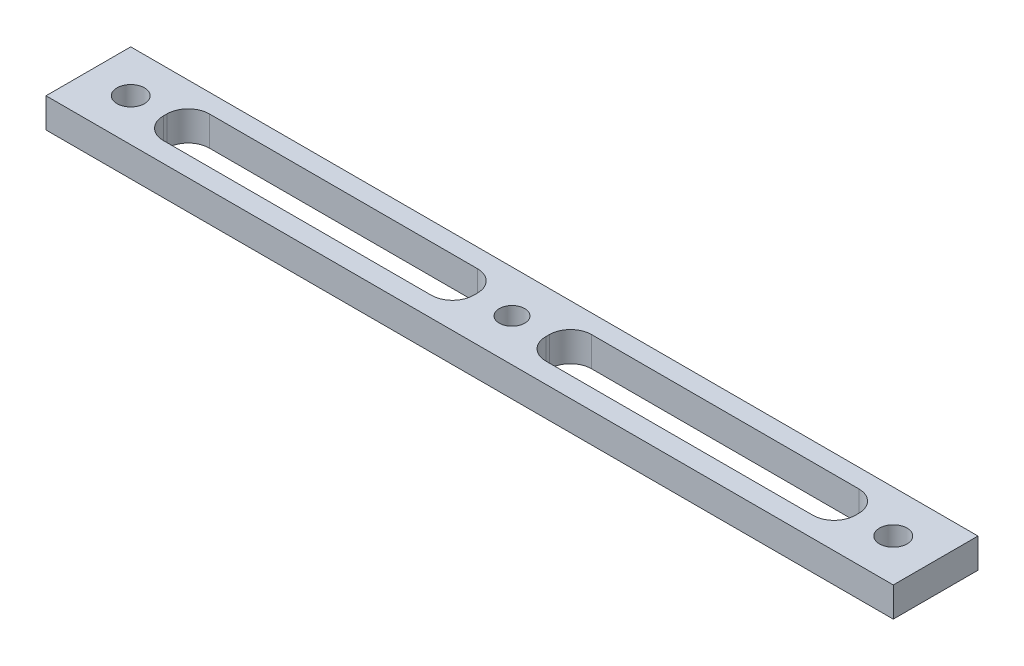
SolidWorks part; units mm, degrees
ref_plane "Płaszczyzna przednia" through (0, 0, 0) normal (0, 0, 1) x (1, 0, 0)
ref_plane "Płaszczyzna górna" through (0, 0, 0) normal (0, 1, 0) x (1, 0, 0)
ref_plane "Płaszczyzna prawa" through (0, 0, 0) normal (1, 0, 0) x (0, 0, -1)
sketch "Szkic1" plane through (0, 0, 0) normal (0, 1, 0) x (1, 0, 0)
  line L0 (100, 0) -> (100, 10)
  line L1 (0, 0) -> (200, 0)
  line L2 (0, 0) -> (0, 20)
  line L3 (0, 20) -> (200, 20)
  line L4 (200, 0) -> (200, 20)
  line L5 (0, 10) -> (10, 10)
  line L6 (200, 10) -> (190, 10)
  line L8 (22.9848, 15.5746) -> (86.2594, 15.5746)
  line L9 (17.9848, 10.5746) -> (17.9848, 9.6967)
  line L10 (22.9848, 4.6967) -> (86.2594, 4.6967)
  line L11 (91.2594, 10.5746) -> (91.2594, 9.6967)
  line L12 (113.2251, 15.5746) -> (176.2862, 15.5746)
  line L13 (108.2251, 10.5746) -> (108.2251, 9.7528)
  line L14 (113.2251, 4.7528) -> (176.2862, 4.7528)
  line L15 (181.2862, 10.5746) -> (181.2862, 9.7528)
  circle A0 centre (100, 10) radius 3
  circle A1 centre (10, 10) radius 3.25
  circle A2 centre (190, 10) radius 3.25
  arc A3 (176.2862, 4.7528) -> (181.2862, 9.7528) centre (176.2862, 9.7528) ccw
  arc A4 (181.2862, 10.5746) -> (176.2862, 15.5746) centre (176.2862, 10.5746) ccw
  arc A5 (113.2251, 4.7528) -> (108.2251, 9.7528) centre (113.2251, 9.7528) cw
  arc A6 (113.2251, 15.5746) -> (108.2251, 10.5746) centre (113.2251, 10.5746) ccw
  arc A7 (17.9848, 9.6967) -> (22.9848, 4.6967) centre (22.9848, 9.6967) ccw
  arc A8 (86.2594, 4.6967) -> (91.2594, 9.6967) centre (86.2594, 9.6967) ccw
  arc A9 (91.2594, 10.5746) -> (86.2594, 15.5746) centre (86.2594, 10.5746) ccw
  arc A10 (22.9848, 15.5746) -> (17.9848, 10.5746) centre (22.9848, 10.5746) ccw
  dimension "D1" = 5
extrude "Dodanie-wyciągnięcie1" add sketch "Szkic1" along normal blind 7 contours A0 L1 L4 L3 L2 region at (50, 0, -2.01)
